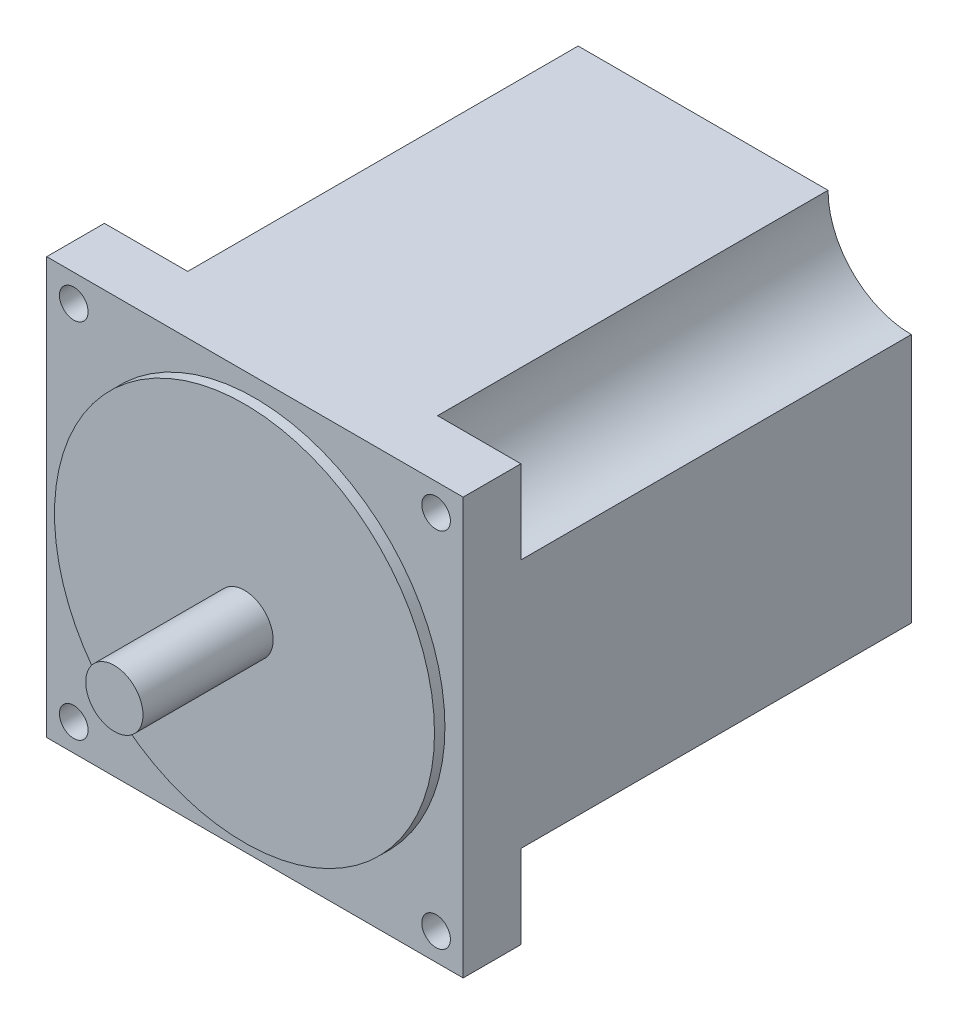
SolidWorks part; units mm, degrees
ref_plane "Front Plane" through (0, 0, 0) normal (0, 0, 1) x (1, 0, 0)
ref_plane "Top Plane" through (0, 0, 0) normal (0, 1, 0) x (1, 0, 0)
ref_plane "Right Plane" through (0, 0, 0) normal (1, 0, 0) x (0, 0, -1)
sketch "Sketch2" plane through (0, 0, 0) normal (0, 0, 1) x (1, 0, 0)
  line L1 (40, -40) -> (-40, -40)
  line L2 (40, -40) -> (40, 40)
  line L3 (40, 40) -> (-40, 40)
  line L4 (-40, -40) -> (-40, 40)
  line L5 (40, -40) -> (-40, 40) construction
  line L6 (40, 40) -> (-40, -40) construction
  point P0 (0, 0)
  dimension "D1" = 80
  dimension "D2" = 80
extrude "Boss-Extrude1" add sketch "Sketch2" along normal blind 86.09 contours L3 L4 L1 L2
sketch "Sketch3" plane through (0, 0, 86.09) normal (0, 0, 1) x (1, 0, 0)
  line L1 (34.8, -34.8) -> (-34.8, -34.8) construction
  line L2 (34.8, -34.8) -> (34.8, 34.8) construction
  line L3 (34.8, 34.8) -> (-34.8, 34.8) construction
  line L4 (-34.8, -34.8) -> (-34.8, 34.8) construction
  line L5 (34.8, -34.8) -> (-34.8, 34.8) construction
  line L6 (34.8, 34.8) -> (-34.8, -34.8) construction
  circle A0 centre (-34.8, 34.8) radius 2.75
  circle A1 centre (34.8, 34.8) radius 2.75
  circle A2 centre (-34.8, -34.8) radius 2.75
  circle A3 centre (34.8, -34.8) radius 2.75
  point P0 (0, 0)
  dimension "D3" = 5.5
  dimension "D4" = 5.5
  dimension "D5" = 5.5
  dimension "D6" = 5.5
  dimension "D1" = 69.6
  dimension "D2" = 69.6
extrude "Cut-Extrude1" cut sketch "Sketch3" against normal through all
sketch "Sketch4" plane through (0, 0, 86.09) normal (0, 0, 1) x (1, 0, 0)
  circle A0 centre (0, 0) radius 36.5
  dimension "D1" = 73
extrude "Boss-Extrude2" add sketch "Sketch4" along normal blind 2
sketch "Sketch5" plane through (0, 0, 88.09) normal (0, 0, 1) x (1, 0, 0)
  circle A0 centre (0, 0) radius 5.5
  dimension "D1" = 11
extrude "Boss-Extrude3" add sketch "Sketch5" along normal blind 25
sketch "Sketch6" plane through (0, 0, 0) normal (0, 0, -1) x (-1, 0, 0)
  line L0 (-40, 40) -> (40, 40) construction
  line L1 (-40, -40) -> (-40, 40) construction
  line L2 (-40, -40) -> (40, -40) construction
  line L3 (40, -40) -> (40, 40) construction
  line L5 (40, -40) -> (-40, -40)
  line L6 (40, -40) -> (40, 40)
  line L7 (40, 40) -> (-40, 40)
  line L8 (-40, -40) -> (-40, 40)
  line L9 (40, -40) -> (-40, 40) construction
  line L10 (40, 40) -> (-40, -40) construction
  arc A0 (-24, 40) -> (-40, 24) centre (-40, 40) cw
  arc A1 (-40, -24) -> (-24, -40) centre (-40, -40) cw
  arc A2 (24, -40) -> (40, -24) centre (40, -40) cw
  arc A3 (24, 40) -> (40, 24) centre (40, 40) ccw
  point P24 (0, 0)
  circle M1 centre (-34.8, 34.8) radius 2.75
  circle M2 centre (34.8, -34.8) radius 2.75
  circle M3 centre (-34.8, -34.8) radius 2.75
  circle M4 centre (34.8, 34.8) radius 2.75
  line M5 (-40, 40) -> (-40, -40)
  line M6 (-40, -40) -> (40, -40)
  line M7 (40, -40) -> (40, 40)
  line M8 (40, 40) -> (-40, 40)
  dimension "D1" = 16
  dimension "D2" = 16
  dimension "D3" = 16
  dimension "D4" = 16
extrude "Cut-Extrude2" cut sketch "Sketch6" against normal blind 75 contours A0 L7 M5 M1 | A3 M8 M7 M4 | A2 M6 M7 M2 | A1 M5 M6 M3 region at (-32, -39.7737, 0) region at (32, -39.7737, 0) region at (-28.8463, 28.8463, 0) region at (39.7737, 32, 0)
sketch "Sketch7" plane through (0, 0, 0) normal (0, 0, -1) x (-1, 0, 0)
  circle A0 centre (0, 0) radius 4.006
  dimension "D1" = 8.012
extrude "Boss-Extrude4" add sketch "Sketch7" along normal blind 13.5
